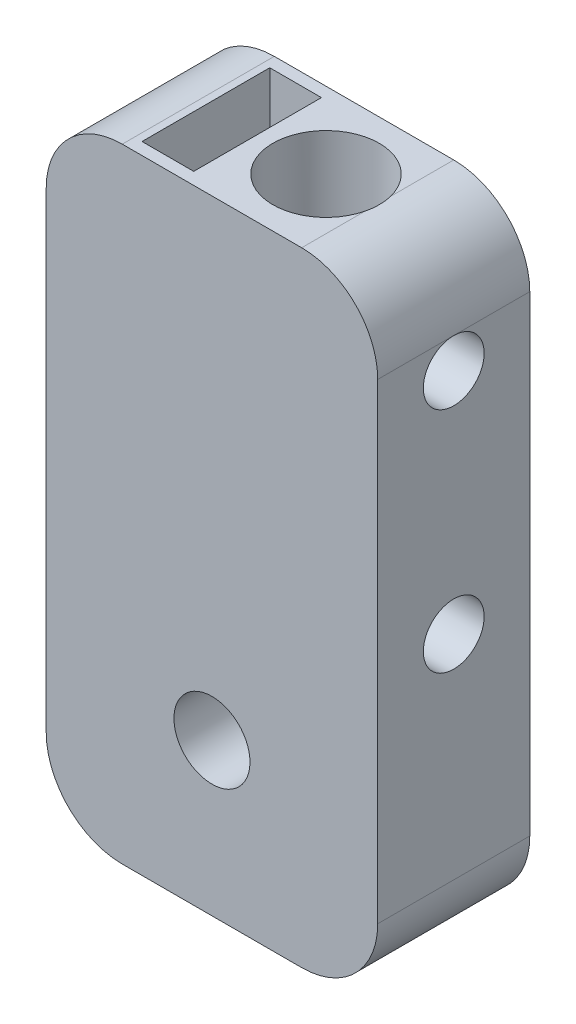
SolidWorks part; units mm, degrees
ref_plane "Alzado" through (0, 0, 0) normal (0, 0, 1) x (1, 0, 0)
ref_plane "Planta" through (0, 0, 0) normal (0, 1, 0) x (1, 0, 0)
ref_plane "Vista lateral" through (0, 0, 0) normal (1, 0, 0) x (0, 0, -1)
sketch "Croquis1" plane through (0, 0, 0) normal (1, 0, 0) x (0, 0, -1)
  line L1 (0, 0) -> (-10, 0)
  line L2 (0, 0) -> (0, -41)
  line L3 (0, -41) -> (-10, -41)
  line L4 (-10, 0) -> (-10, -41)
  dimension "D1" = 10
  dimension "D2" = 41
extrude "Saliente-Extruir1" add sketch "Croquis1" along normal blind 21.8 contours L2 L3 L4 L1
sketch "Croquis6" plane through (0, 0, 0) normal (-1, 0, 0) x (0, 0, 1)
  line L1 (5, -7) -> (5, 0) construction
  line L2 (5, -22) -> (5, -7) construction
  line L3 (0, 0) -> (10, 0) construction
  circle A0 centre (5, -22) radius 2
  circle A1 centre (5, -7) radius 2
  dimension "D1" = 15
  dimension "D3" = 4
  dimension "D4" = 4
  dimension "D2" = 7
extrude "Cortar-Extruir2" cut sketch "Croquis6" against normal up to surface (21.8 mm away) up to face at (21.8, -20.5, 5)
sketch "Croquis7" plane through (21.8, 0, 0) normal (1, 0, 0) x (0, 0, -1)
  line L2 (-5, -22) -> (-5, -7) construction
  circle A0 centre (-5, -22) radius 3.5
  circle A1 centre (-5, -7) radius 3.5
  circle A2 centre (-5, -7) radius 2 construction
  dimension "D1" = 7
  dimension "D2" = 7
  dimension "D3" = 15
sketch "Croquis11" plane through (0, -41, 0) normal (0, -1, 0) x (1, 0, 0)
  line L0 (13.4, 0) -> (13.4, 5) construction
  line L1 (0, 0) -> (0, 10) construction
  line L2 (0, 0) -> (0, 10) construction
  line L7 (16.9, 5) -> (21.8, 5) construction
  line L8 (13.4, 5) -> (8.9, 5) construction
  line L9 (8.9, 9.2) -> (5.5, 9.2)
  line L14 (8.9, 9.2) -> (8.9, 0.8)
  line L16 (8.9, 0.8) -> (5.5, 0.8)
  line L17 (5.5, 9.2) -> (5.5, 0.8)
  line L18 (21.8, 0) -> (21.8, 10) construction
  line L19 (5.5, 5) -> (0, 5) construction
  circle A1 centre (13.4, 5) radius 3.5
  dimension "D1" = 8.4
  dimension "D2" = 5.5
  dimension "D3" = 5
  dimension "D4" = 3.4
  dimension "D5" = 4.5
extrude "Cortar-Extruir4" cut sketch "Croquis11" against normal up to next
sketch "Croquis12" plane through (0, 0, 0) normal (0, 0, -1) x (-1, 0, 0)
  line L0 (-10.9, -31) -> (-10.9, -41) construction
  line L2 (-21.8, -41) -> (0, -41) construction
  circle A0 centre (-10.9, -31) radius 2.5
  dimension "D1" = 5
  dimension "D2" = 10
extrude "Cortar-Extruir5" cut sketch "Croquis12" against normal up to surface (10 mm away) up to face at (10.9, -20.5, 10)
fillet "Redondeo1" radius 5 4 edges at (21.8, -41, 5) (0, -41, 5) (21.8, 0, 5) (0, 0, 5)
sketch "Croquis13" plane through (0, 0, 0) normal (-1, 0, 0) x (0, 0, 1)
  line L0 (5, -7) -> (5, -22) construction
  line L1 (5, -14.5) -> (2.8317, -14.5) construction
  circle A0 centre (5, -22) radius 2 construction
  circle A1 centre (5, -7) radius 2 construction
  circle A2 centre (5, -22) radius 2 construction
  circle A3 centre (5, -7) radius 2 construction
  circle A4 centre (5, -7) radius 3.5
  circle A5 centre (5, -22) radius 3.5
  dimension "D1" = 7
extrude "Cortar-Extruir6" cut sketch "Croquis13" against normal blind 3.5
sketch "Croquis14" plane through (0, 0, 10) normal (0, 0, 1) x (1, 0, 0)
  circle A0 centre (10.9, -31) radius 6.5
  dimension "D1" = 13
sketch "Croquis15" plane through (0, -41, 0) normal (0, -1, 0) x (1, 0, 0)
  line L0 (5.5, 0.8) -> (8.9, 0.8) construction
  line L1 (8.9, 0.8) -> (8.9, 9.2) construction
  line L2 (8.9, 9.2) -> (5.5, 9.2) construction
  line L3 (5.5, 9.2) -> (5.5, 0.8) construction
  line L4 (5.5, 0.8) -> (8.9, 0.8)
  line L5 (8.9, 0.8) -> (8.9, 9.2)
  line L6 (8.9, 9.2) -> (5.5, 9.2)
  line L7 (5.5, 9.2) -> (5.5, 0.8)
  arc A0 (16.8, 4.1693) -> (16.8, 5.8307) centre (13.4, 5) ccw construction
  arc A1 (16.8, 5.8307) -> (16.8, 4.1693) centre (13.4, 5) ccw construction
  arc A2 (16.8, 4.1693) -> (16.8, 5.8307) centre (13.4, 5) ccw
  arc A3 (16.8, 5.8307) -> (16.8, 4.1693) centre (13.4, 5) ccw
extrude "Saliente-Extruir2" add sketch "Croquis15" against normal blind 13
sketch "Croquis16" plane through (0, 0, 10) normal (0, 0, 1) x (1, 0, 0)
  circle A0 centre (10.9, -31) radius 2.5 construction
  circle A1 centre (10.9, -31) radius 2.5
extrude "Cortar-Extruir7" cut sketch "Croquis16" against normal up to surface (10 mm away) up to face at (10.9, -28.5, 0)
